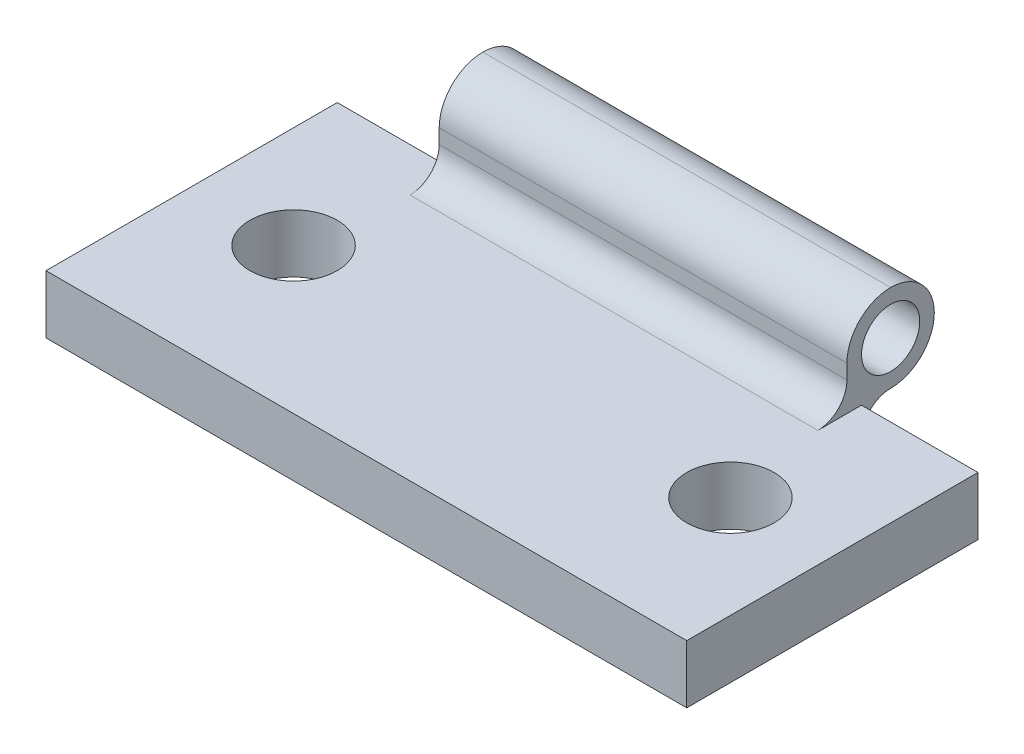
SolidWorks part; units mm, degrees
ref_plane "Front Plane" through (0, 0, 0) normal (0, 0, 1) x (1, 0, 0)
ref_plane "Top Plane" through (0, 0, 0) normal (0, 1, 0) x (1, 0, 0)
ref_plane "Right Plane" through (0, 0, 0) normal (1, 0, 0) x (0, 0, -1)
sketch "Sketch2" plane through (0, 0, 0) normal (0, 1, 0) x (1, 0, 0)
  line L1 (-11, 5) -> (11, 5)
  line L2 (-11, 5) -> (-11, -5)
  line L3 (-11, -5) -> (11, -5)
  line L4 (11, 5) -> (11, -5)
  line L5 (-11, 5) -> (11, -5) construction
  line L6 (-11, -5) -> (11, 5) construction
  circle A0 centre (-7.5, 0) radius 1.5
  circle A1 centre (7.5, 0) radius 1.5
  point P0 (0, 0)
  dimension "D3" = 15
  dimension "D4" = 0
  dimension "D5" = 3
  dimension "D6" = 5
  dimension "D7" = 7.5
  dimension "D1" = 22
  dimension "D2" = 10
extrude "Boss-Extrude1" add sketch "Sketch2" along normal blind 2
sketch "Sketch3" plane through (0, 0, 0) normal (1, 0, 0) x (0, 0, -1)
  line L0 (5, 2) -> (5, 0) construction
  line L1 (7.5, 2) -> (4.5, 2)
  line L2 (7.5, 2) -> (7.5, 5)
  line L3 (7.5, 5) -> (4.5, 5)
  line L4 (4.5, 2) -> (4.5, 5)
  line L5 (-5, 2) -> (5, 2) construction
  circle A0 centre (6, 3.5) radius 1
  point P9 (4.5, 3.5)
  dimension "D3" = 1.5
  dimension "D4" = 1.5
  dimension "D5" = 2
  dimension "D1" = 3
  dimension "D2" = 3
  dimension "D6" = 0.5
  dimension "D7" = 0
extrude "Boss-Extrude2" add sketch "Sketch3" along normal mid plane 14
fillet "Fillet1" radius 1.5 2 edges at (0, 5, -4.5) (0, 5, -7.5)
fillet "Fillet2" radius 1 2 edges at (0, 2, -5) (0, 2, -4.5)
fillet "Fillet3" radius 1.5 1 edges at (0, 2, -7.5)
